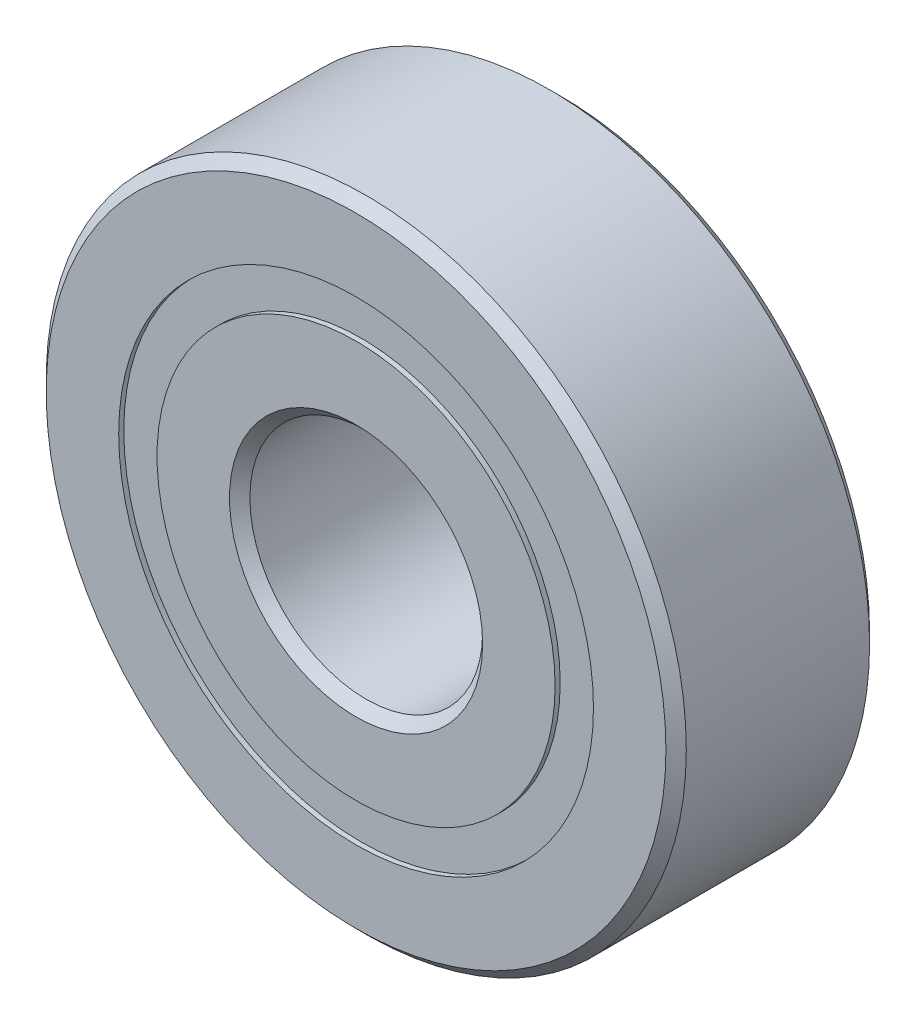
SolidWorks part; units mm, degrees
material "AISI 316 Annealed Stainless Steel Bar (SS)"
ref_plane "Front Plane" through (0, 0, 0) normal (0, 0, 1) x (1, 0, 0)
ref_plane "Top Plane" through (0, 0, 0) normal (0, 1, 0) x (1, 0, 0)
ref_plane "Right Plane" through (0, 0, 0) normal (1, 0, 0) x (0, 0, -1)
sketch "Sketch1" plane through (0, 0, 0) normal (1, 0, 0) x (0, 0, -1)
  line L0 (-3.5, 0) -> (3.5, 0) construction
  line L1 (0, 11) -> (0, -11) construction
  line L2 (3.15, 11) -> (-3.15, 11)
  line L3 (-3.15, 11) -> (-3.5, 10.65)
  line L4 (-3.5, 10.65) -> (-3.5, 8.1593)
  line L5 (-3.5, 8.1593) -> (-1.5556, 8.1593)
  line L6 (3.5, 8.1593) -> (1.5556, 8.1593)
  line L7 (3.5, 10.65) -> (3.5, 8.1593)
  line L8 (3.15, 11) -> (3.5, 10.65)
  line L9 (0, 11) -> (0, 7.5) construction
  line L10 (0, 7.5) -> (0, 4) construction
  arc A0 (-1.5556, 8.1593) -> (1.5556, 8.1593) centre (0, 7.5) cw
  point P14 (0, 4)
  dimension "Width" = 7
  dimension "OD" = 22
  dimension "D1" = 45
  dimension "D2" = 0.35
  dimension "Shaft Dia" = 8
  dimension "D3" = 3.1111
  dimension "D4" = 0.6593
revolve "Revolve1" add sketch "Sketch1" angle 360 about L0
sketch "Sketch3" plane through (0, 0, 0) normal (1, 0, 0) x (0, 0, -1)
  line L0 (-3.5, 6.8407) -> (-1.5556, 6.8407)
  line L1 (0, 11) -> (0, -11) construction
  line L2 (-3.5, 10.65) -> (-3.5, 8.1593) construction
  line L3 (-3.5, 6.8407) -> (-3.5, 4.35)
  line L4 (-3.15, 11) -> (-3.5, 10.65) construction
  line L5 (-3.5, 4.35) -> (-3.15, 4)
  line L6 (-3.15, 4) -> (3.15, 4)
  line L7 (3.15, 11) -> (3.15, -11) construction
  line L8 (3.15, 4) -> (3.5, 4.35)
  line L9 (3.5, -10.65) -> (3.5, 10.65) construction
  line L10 (3.5, 4.35) -> (3.5, 6.8407)
  line L11 (3.5, 6.8407) -> (1.5556, 6.8407)
  line L13 (3.15, 11) -> (3.5, 10.65) construction
  arc A0 (1.5556, 8.1593) -> (-1.5556, 8.1593) centre (0, 7.5) ccw construction
  arc A1 (1.5556, 6.8407) -> (-1.5556, 6.8407) centre (0, 7.5) cw
revolve "Revolve3" add sketch "Sketch3" angle 360 about L0
sketch "Sketch4" plane through (0, 0, 0) normal (1, 0, 0) x (0, 0, -1)
  line L0 (-1.6895, 7.5) -> (1.6895, 7.5)
  arc A2 (-1.6895, 7.5) -> (1.6895, 7.5) centre (0, 7.5) cw
  arc A3 (1.5556, 8.1593) -> (-1.5556, 8.1593) centre (0, 7.5) ccw construction
revolve "Revolve4" add sketch "Sketch4" angle 360 about L0
ref_axis "Axis1" through (0, 0, -3.5) along (0, 0, 1)
pattern_circular "CirPattern1" count 10 every 36 about axis through (0, 0, -3.5) along (0, 0, 1) of bodies 104
sketch "Sketch6" plane through (0, 0, 0) normal (1, 0, 0) x (0, 0, -1)
  line L0 (-3.5, 8.1593) -> (-1.5556, 8.1593) construction
  line L1 (-3.325, 8.1593) -> (-1.6895, 8.1593)
  line L2 (-3.325, 8.1593) -> (-3.325, 6.8407)
  line L3 (-3.325, 6.8407) -> (-1.6895, 6.8407)
  line L4 (-1.6895, 8.1593) -> (-1.6895, 6.8407)
  line L5 (-3.5, 6.8407) -> (-1.5556, 6.8407) construction
  line L6 (3.5, 8.1593) -> (1.5556, 8.1593) construction
  line L7 (3.325, 8.1593) -> (1.6895, 8.1593)
  line L8 (3.325, 8.1593) -> (3.325, 6.8407)
  line L9 (3.325, 6.8407) -> (1.6895, 6.8407)
  line L10 (1.6895, 8.1593) -> (1.6895, 6.8407)
  line L11 (3.5, 6.8407) -> (1.5556, 6.8407) construction
  line L12 (-3.15, 11) -> (-3.5, 10.65) construction
  point P18 (-3.325, 10.825)
revolve "Revolve5" add sketch "Sketch6" angle 360 about L0
equation "\"D2@Sketch1\" = \"Width@Sketch1\"*.05"
equation "\"D3@Sketch1\" = \"Width@Sketch1\"/2.25"
equation "\"D4@Sketch1\" = (((\"OD@Sketch1\"-\"Width@Sketch1\")/2)/3.25)/3.5"
equation "\"D2@CirPattern1\" = 360/\"Balls@CirPattern1\""
